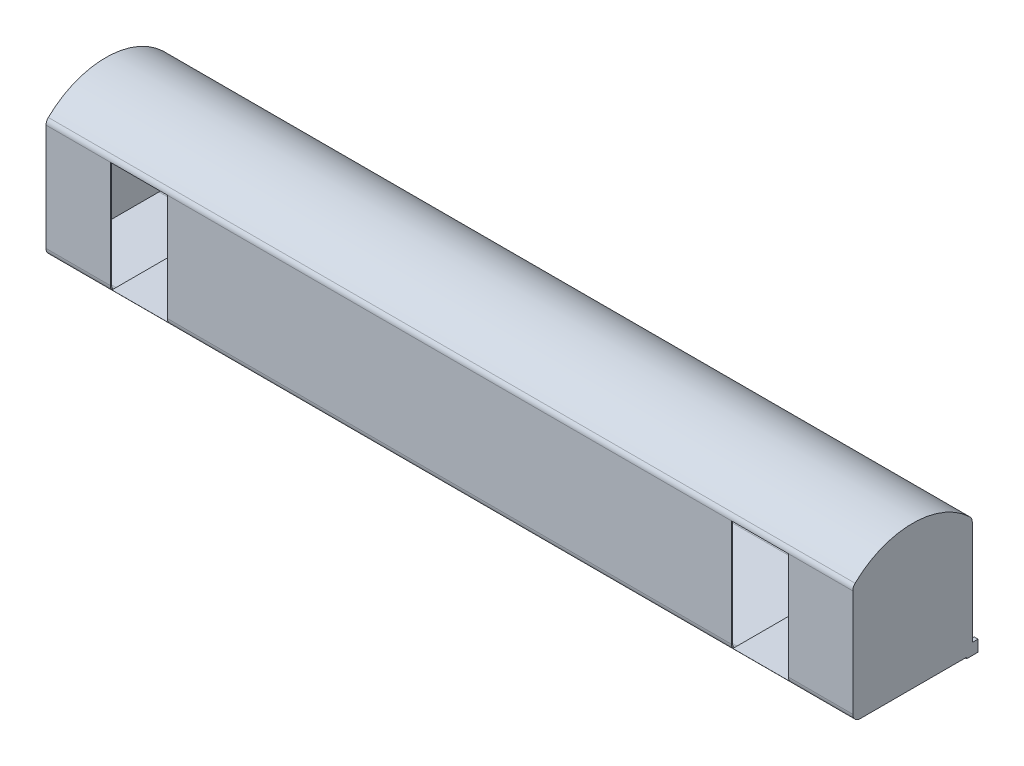
SolidWorks part; units mm, degrees
ref_plane "Front Plane" through (0, 0, 0) normal (0, 0, 1) x (1, 0, 0)
ref_plane "Top Plane" through (0, 0, 0) normal (0, 1, 0) x (1, 0, 0)
ref_plane "Right Plane" through (0, 0, 0) normal (1, 0, 0) x (0, 0, -1)
sketch "Sketch1" plane through (0, 0, 0) normal (1, 0, 0) x (0, 0, -1)
  line L5 (-1376, -1550) -> (1376, -1550)
  line L6 (-1576, -1350) -> (-1576, 1467.4388)
  line L8 (1576, -1350) -> (1576, 1467.4388)
  line L9 (-1576, -1550) -> (1576, 1550) construction
  line L10 (-1576, 1550) -> (1576, -1550) construction
  arc A1 (1514.8635, 1611.3725) -> (-1514.8635, 1611.3725) centre (0, 41.1984) ccw
  arc A2 (1514.8635, 1611.3725) -> (1576, 1467.4388) centre (1376, 1467.4388) cw
  arc A3 (-1576, 1467.4388) -> (-1514.8635, 1611.3725) centre (-1376, 1467.4388) cw
  arc A4 (1376, -1550) -> (1576, -1350) centre (1376, -1350) ccw
  arc A5 (-1376, -1550) -> (-1576, -1350) centre (-1376, -1350) cw
  point P0 (0, 0)
  point P6 (0, 2223)
  dimension "D5" = 200
  dimension "D6" = 200
  dimension "D1" = 3152
  dimension "D2" = 3773
  dimension "D3" = 3100
  dimension "D4" = 0
extrude "Boss-Extrude1" add sketch "Sketch1" along normal blind 21279 contours A1 A3 L6 A5 L5 A4 L8 A2
sketch "Sketch2" plane through (0, 0, -1576) normal (0, 0, -1) x (-1, 0, 0)
  line L0 (-21279, 1467.4388) -> (0, 1467.4388) construction
  line L1 (-18079, -1467.4388) -> (-19579, -1467.4388)
  line L2 (-18079, -1467.4388) -> (-18079, 1467.4388)
  line L3 (-18079, 1467.4388) -> (-19579, 1467.4388)
  line L4 (-19579, -1467.4388) -> (-19579, 1467.4388)
  line L5 (-18079, -1467.4388) -> (-19579, 1467.4388) construction
  line L6 (-18079, 1467.4388) -> (-19579, -1467.4388) construction
  line L7 (-21279, -1350) -> (-21279, 1467.4388) construction
  line L8 (0, -1350) -> (0, 1467.4388) construction
  line L9 (-1700, -1467.4388) -> (-3200, -1467.4388)
  line L10 (-1700, -1467.4388) -> (-1700, 1467.4388)
  line L11 (-1700, 1467.4388) -> (-3200, 1467.4388)
  line L12 (-3200, -1467.4388) -> (-3200, 1467.4388)
  line L13 (-1700, -1467.4388) -> (-3200, 1467.4388) construction
  line L14 (-1700, 1467.4388) -> (-3200, -1467.4388) construction
  point P0 (-18829, 0)
  point P9 (-2450, 0)
  dimension "D1" = 1500
  dimension "D2" = 1700
  dimension "D3" = 1500
  dimension "D4" = 1700
extrude "Cut-Extrude1" cut sketch "Sketch2" against normal up to surface (3152 mm away) up to face at (10639.5, 58.7194, 1576)
shell "Shell1" thickness 30 removed face at (19579, -451.0048, 0) removed face at (3200, -451.0048, 0) removed face at (1700, -451.0048, 0) removed face at (18079, -451.0048, 0)
sketch "Sketch3" plane through (0, 0, -1576) normal (0, 0, -1) x (-1, 0, 0)
  line L0 (-18079, -1467.4388) -> (-19579, -1467.4388) construction
  line L1 (-19579, -2967.4388) -> (-19529, -2967.4388)
  line L2 (-19579, -2967.4388) -> (-19579, -1467.4388)
  line L3 (-19579, -1467.4388) -> (-19529, -1467.4388)
  line L4 (-19529, -2967.4388) -> (-19529, -2867.4388)
  line L5 (-19579, -2967.4388) -> (-19529, -1467.4388) construction
  line L6 (-19579, -1467.4388) -> (-19529, -2967.4388) construction
  line L7 (-19579, 1467.4388) -> (-19579, -1350) construction
  line L8 (-19529, -1917.4388) -> (-18129, -1917.4388)
  line L9 (-18129, -2967.4388) -> (-18079, -2967.4388)
  line L10 (-18129, -2967.4388) -> (-18129, -2867.4388)
  line L11 (-18129, -1467.4388) -> (-18079, -1467.4388)
  line L12 (-18079, -2967.4388) -> (-18079, -1467.4388)
  line L13 (-18129, -2967.4388) -> (-18079, -1467.4388) construction
  line L14 (-18129, -1467.4388) -> (-18079, -2967.4388) construction
  line L15 (-19529, -1967.4388) -> (-18129, -1967.4388)
  line L16 (-19529, -2367.4388) -> (-18129, -2367.4388)
  line L17 (-19529, -2417.4388) -> (-18129, -2417.4388)
  line L18 (-19529, -2817.4388) -> (-18129, -2817.4388)
  line L19 (-19529, -2867.4388) -> (-18129, -2867.4388)
  line L20 (-19529, -1917.4388) -> (-19529, -1467.4388)
  line L21 (-19529, -2367.4388) -> (-19529, -1967.4388)
  line L22 (-19529, -2817.4388) -> (-19529, -2417.4388)
  line L23 (-18129, -2817.4388) -> (-18129, -2417.4388)
  line L24 (-18129, -2367.4388) -> (-18129, -1967.4388)
  line L25 (-18129, -1917.4388) -> (-18129, -1467.4388)
  point P0 (-19554, -2217.4388)
  point P9 (-18104, -2217.4388)
  dimension "D1" = 1500
  dimension "D2" = 0
  dimension "D3" = 50
  dimension "D4" = 50
  dimension "D5" = 1500
  dimension "D6" = 50
  dimension "D7" = 450
  dimension "D8" = 3
extrude "Boss-Extrude2" add sketch "Sketch3" against normal mid plane 300
sketch "Sketch4" plane through (19579, 0, 0) normal (-1, 0, 0) x (0, 0, 1)
  line L0 (-1490.2983, -1377.178) -> (-1494.2248, -1377.178)
  line L1 (-1694.2248, -1177.178) -> (-1694.2248, 1186.0259)
  line L2 (-1494.2248, 1386.0259) -> (-1490.2983, 1386.0259)
  arc A0 (-1494.2248, -1377.178) -> (-1694.2248, -1177.178) centre (-1494.2248, -1177.178) cw
  arc A1 (-1694.2248, 1186.0259) -> (-1494.2248, 1386.0259) centre (-1494.2248, 1186.0259) cw
  dimension "D1" = 200
sweep "Sweep1" add path "Sketch4" circular profile diameter 100 parameters "D3"=100
pattern_linear "LPattern1" count 2 spacing 1500 along (-1, 0, 0) of "Sweep1"
sketch "Sketch23" plane through (21279, 0, 0) normal (1, 0, 0) x (0, 0, -1)
  line L1 (1427.2141, -1585.8071) -> (1727.2141, -1585.8071)
  line L2 (1427.2141, -1585.8071) -> (1427.2141, -1285.8071)
  line L3 (1427.2141, -1285.8071) -> (1727.2141, -1285.8071)
  line L4 (1727.2141, -1585.8071) -> (1727.2141, -1285.8071)
  line L5 (1427.2141, -1585.8071) -> (1727.2141, -1285.8071) construction
  line L6 (1427.2141, -1285.8071) -> (1727.2141, -1585.8071) construction
  point P0 (1577.2141, -1435.8071)
  point P5 (1577.2141, -1435.8071)
  dimension "D1" = 300
  dimension "D2" = 300
extrude "Boss-Extrude3" add sketch "Sketch23" against normal blind 100
pattern_linear "LPattern2" count 2 spacing 3330 along (-1, 0, 0) of "Boss-Extrude3"
sketch "Sketch24" plane through (21179, 19.0832, -13.6947) normal (-1, 0, 0) x (0, 0, 1)
  circle A0 centre (-1636.9259, -1440.7902) radius 35
  point P2 (-1618.7412, -1436.5661)
  point P3 (-1636.9259, -1440.7902)
  dimension "D1" = 70
extrude "Boss-Extrude4" add sketch "Sketch24" along normal up to surface (3230 mm away) up to face at (17949, -1443.6453, -1582.2911)
